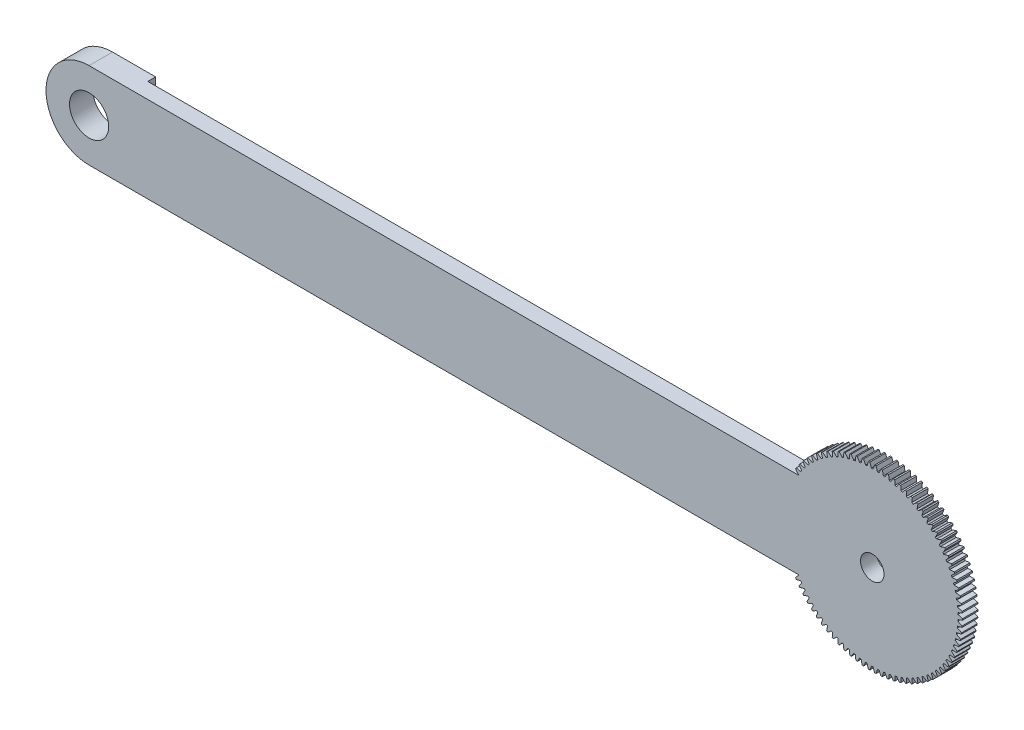
SolidWorks part; units mm, degrees
material "Alumina"
ref_plane "Plane1" through (0, 0, 0) normal (0, 0, 1) x (1, 0, 0)
ref_plane "Plane2" through (0, 0, 0) normal (0, 1, 0) x (1, 0, 0)
ref_plane "Plane3" through (0, 0, 0) normal (1, 0, 0) x (0, 0, -1)
sketch "HoldingSke" plane through (0, 0, 0) normal (0, 1, 0) x (1, 0, 0)
  line L0 (0, 0) -> (0, -2)
  line L1 (-15, 0) -> (100, 0) construction
  line L2 (0, 0) -> (-2.1039, 2.3779)
  line L3 (0, 0) -> (-11.863, 4.5341)
  line L4 (0, 0) -> (0, 8.636)
  line L5 (0, 0) -> (-46.8476, -17.4728)
  line L6 (0, 0) -> (-3.3159, -2.2372)
  line L7 (-2.1039, 2.3779) -> (8.6586, 51.2059)
  line L8 (-76.2, 54.61) -> (-74.4, 54.61)
  line L9 (-71.009, 38.7566) -> (-53.1078, 45.2721)
  line L10 (-76.2, 71.12) -> (104.1128, 71.12)
  line L11 (0, 0) -> (-4, 0)
  line L12 (-76.2, 101.6) -> (-76.181, 101.6)
  line L13 (24.9733, 27.94) -> (52.9518, 28.4284)
  line L14 (24.9733, 27.94) -> (24.9743, 27.94)
  line L15 (24.9733, 27.94) -> (100.4006, 29.5858)
  line L16 (-63.627, -0.5) -> (-12.827, -0.5)
  circle A0 centre (0, 0) radius 5
  circle A1 centre (0, 0) radius 21.874
  circle A2 centre (0, 0) radius 37.5
  circle A3 centre (0, 0) radius 5
  dimension "MHD" = 43.748
  dimension "Hub_dia" = 75
  dimension "Bore" = 10
  dimension "MBD" = 10
  dimension "Num_teeth" = 90
  dimension "Pitch" = 2
  dimension "Overall_len" = 50
  dimension "Show_teeth" = 90
  dimension "Thickness" = 4
  dimension "OAL" = 50.0001
  dimension "T_dim" = 1.8
  dimension "Ap" = 20
  dimension "H" = 19.05
  dimension "Pitch_radius" = 180.3128
  dimension "Width" = 4
  dimension "Backlash" = 0.019
  dimension "Addendum_fac" = 1
  dimension "Dedendum_fac" = 1.25
  dimension "Clearance_fac" = 0.25
  dimension "Dedendum_add" = 0.001
  dimension "Module" = 0.5
sketch "BasProSke" plane through (0, 0, 0) normal (0, 1, 0) x (1, 0, 0)
  line L0 (-10, 0) -> (60, 0) construction
  line L1 (0, 0) -> (0, 23)
  line L2 (0, 0) -> (4, 0)
  line L3 (4, 0) -> (4, 23)
  line L4 (4, 23) -> (0, 23)
  dimension "Thickness" = 4
  dimension "Diameter" = 46
revolve "Base-Revolve" add sketch "BasProSke" angle 360 about L0
sketch "TooCutSke" plane through (0, 0, 0) normal (1, 0, 0) x (0, 0, -1)
  line L1 (0, 0) -> (0, 107) construction
  line L2 (0, 0) -> (-0.4259, 22.496) construction
  line L3 (0, 0) -> (-1.5703, 44.9668) construction
  line L4 (-0.4259, 22.496) -> (-0.7851, 22.4834) construction
  arc A0 (0.2085, 21.873) -> (-0.2085, 21.873) centre (0, 0) ccw
  arc A1 (0.6483, 23.0163) -> (-0.6483, 23.0163) centre (0, 0) ccw
  circle A2 centre (0, 0) radius 22.5 construction
  circle A3 centre (0, 0) radius 21.1431 construction
  arc A4 (-0.2085, 21.873) -> (-0.6483, 23.0163) centre (-8.8088, 19.2207) ccw
  arc A5 (0.6483, 23.0163) -> (0.2085, 21.873) centre (8.8088, 19.2207) ccw
  dimension "Root_dia" = 43.748
  dimension "Overcut_dia" = 46.0508
  dimension "Pitch_dia" = 45
  dimension "Base_dia" = 42.2862
  dimension "Flank_rad" = 9
  dimension "Half_ang" = 2
  dimension "Half_CT" = 0.3594
extrude "ToothCut" cut sketch "TooCutSke" along normal through all
fillet "Breaks" [suppressed] radius 0.01 tangent propagation no
fillet "RootFillets" [suppressed] radius 0.126
pattern_circular "TeethCuts" count 90 every 4 about axis through (-10, 0, 0) along (1, 0, 0) of "ToothCut", "RootFillets", "Breaks"
sketch "HubNeaOneSke" plane through (0, 0, 0) normal (-1, 0, 0) x (0, 0, 1)
  circle A0 centre (0, 0) radius 21.874
  dimension "Diameter" = 43.748
extrude "HubNearOne" [suppressed] add sketch "HubNeaOneSke" along normal blind 46.0001
sketch "HubNeaBotSke" plane through (0, 0, 0) normal (-1, 0, 0) x (0, 0, 1)
  circle A0 centre (0, 0) radius 21.874
  dimension "Diameter" = 43.748
extrude "HubNearBoth" [suppressed] add sketch "HubNeaBotSke" along normal blind 23
ref_plane "FarPln" through (4, 0, 0) normal (1, 0, 0) x (0, 0, -1)
sketch "HubFarSke" plane through (4, 0, 0) normal (1, 0, 0) x (0, 0, -1)
  circle A0 centre (0, 0) radius 21.874
  dimension "Diameter" = 43.748
extrude "HubFar" [suppressed] add sketch "HubFarSke" along normal blind 23
sketch "BorSke" plane through (0, 0, 0) normal (1, 0, 0) x (0, 0, -1)
  circle A0 centre (0, 0) radius 5
  dimension "Diameter" = 10
extrude "Bore" cut sketch "BorSke" along normal mid plane 100.0001
sketch "KeySke" plane through (0, 0, 0) normal (1, 0, 0) x (0, 0, -1)
  line L0 (-2, 0) -> (-2, 6.8)
  line L1 (-2, 6.8) -> (2, 6.8)
  line L2 (2, 6.8) -> (2, 0)
  line L3 (0, 0) -> (0, 34) construction
  line L4 (-2, 0) -> (2, 0)
  dimension "Width" = 4
  dimension "Offset" = 6.8
extrude "Keyway" [suppressed] cut sketch "KeySke" along normal mid plane 100.0001
pattern_circular "Keyway2" [suppressed] count 2 every 90 about axis through (-10, 0, 0) along (1, 0, 0) reverse direction yes
sketch "Sketch1" plane through (0, 0, 0) normal (1, 0, 0) x (0, 0, -1)
  line L0 (0, 0) -> (-200, 0) construction
  line L1 (0, -11) -> (-200, -11)
  line L2 (0, 11) -> (-200, 11)
  arc A0 (0, -11) -> (0, 11) centre (0, 0) ccw
  arc A1 (-200, 11) -> (-200, -11) centre (-200, 0) ccw
  point P3 (-100, 0)
extrude "Boss-Extrude1" add sketch "Sketch1" along normal blind 4 contours L2 A1 L1 A0
sketch "Sketch3" plane through (0, 0, 0) normal (1, 0, 0) x (0, 0, -1)
  circle A2 centre (-200, 0) radius 5
extrude "Cut-Extrude2" cut sketch "Sketch3" along normal through all contours A2 region at (0, 0, 200)
sketch "Sketch4" plane through (0, 0, 0) normal (1, 0, 0) x (0, 0, -1)
  circle A0 centre (0, 0) radius 3
extrude "Cut-Extrude4" cut sketch "Sketch4" along normal through all
move or copy body "Body-Move/Copy1" bodies to move or copy 106 copy no rotation origin (2, 0, 94) rotation axis (0, 1, 0) rotation angle 90
move or copy body "Body-Move/Copy2" bodies to move or copy 107 copy no rotation origin (2, 0, 0) rotation axis (0, 0, 1) rotation angle 180
sketch "Sketch5" plane through (0, 0, 92) normal (0, 0, -1) x (-1, 0, 0)
  line L1 (93, 11) -> (93, -11)
  line L2 (-77.0931, 11) -> (104, 11) construction
  line L3 (-77.0931, -11) -> (104, -11) construction
  line L4 (93, 11) -> (104, 11)
  line L5 (93, -11) -> (104, -11)
  arc A1 (104, -11) -> (104, 11) centre (104, 0) ccw construction
  circle A2 centre (104, 0) radius 5 construction
  circle A3 centre (104, 0) radius 5
  arc A4 (104, -11) -> (104, 11) centre (104, 0) ccw
extrude "Boss-Extrude2" add sketch "Sketch5" along normal blind 2
ref_axis "Axis1" through (96, 0, 63.756) along (0, 0, 1)
equation "' \"Module@HoldingSke\" = 6.35"
equation "' \"Num_teeth@HoldingSke\" = 12"
equation "' \"Ap@HoldingSke\" =  20"
equation "' \"Ap@HoldingSke\" = 20"
equation "' \"Width@HoldingSke\" = 0.5 * 25.4"
equation "' \"Hub_dia@HoldingSke\"= 1 * 25.4"
equation "' \"Hub_dia@HoldingSke\" = 1 * 25.4"
equation "' \"Overall_len@HoldingSke\" = 1.0 * 25.4"
equation "' \"Bore@HoldingSke\" = 0.75 * 25.4"
equation "' \"T_dim@HoldingSke\" = 0.1 * 25.4"
equation "' \"Width@KeySke\" = 0.25 * 25.4"
equation "' \"Show_teeth@HoldingSke\" = 13"
equation "' \"Backlash@HoldingSke\" = 0.009 * 25.4"
equation "' \"Addendum_fac@HoldingSke\" = 1.0"
equation "' \"Dedendum_fac@HoldingSke\" = 1.25"
equation "' \"Dedendum_add@HoldingSke\" = 0.00005 * 25.4"
equation "' \"Clearance_fac@HoldingSke\" = 0.25"
equation "\"Pitch@HoldingSke\" = 1 / \"Module@HoldingSke\""
equation "\"Overcut_dia@TooCutSke\" = (\"Num_teeth@HoldingSke\" + 2 * \"Addendum_fac@HoldingSke\") / \"Pitch@HoldingSke\" + 0.002 * 25.4"
equation "\"Pitch_dia@TooCutSke\" = \"Num_teeth@HoldingSke\" / \"Pitch@HoldingSke\""
equation "\"Base_dia@TooCutSke\" = \"Num_teeth@HoldingSke\" / \"Pitch@HoldingSke\" * cos((\"Ap@HoldingSke\"  * 3.14159265 / 180))"
equation "\"Root_dia@TooCutSke\" = (\"Num_teeth@HoldingSke\" + 2) / \"Pitch@HoldingSke\" - 2 * (\"Addendum_fac@HoldingSke\" + \"Dedendum_fac@HoldingSke\") / \"Pitch@HoldingSke\" - \"Dedendum_add@HoldingSke\" * 2"
equation "\"Half_ang@TooCutSke\" = 180 / \"Num_teeth@HoldingSke\""
equation "\"Half_CT@TooCutSke\" = \"Num_teeth@HoldingSke\" / \"Pitch@HoldingSke\" * sin((3.14159265 / 2 / \"Num_teeth@HoldingSke\")) / 2 - 7 * \"Backlash@HoldingSke\" / 4"
equation "\"Flank_rad@TooCutSke\" = \"Num_teeth@HoldingSke\" / \"Pitch@HoldingSke\" / 5"
equation "\"Radius@RootFillets\" = \"Clearance_fac@HoldingSke\" / \"Pitch@HoldingSke\" + \"Dedendum_add@HoldingSke\""
equation "\"Break_rad@Breaks\" = 0.02 / \"Pitch@HoldingSke\""
equation "\"Thickness@HoldingSke\" = \"Width@HoldingSke\""
equation "\"OAL@HoldingSke\" = \"Thickness@HoldingSke\""
equation "\"MHD@HoldingSke\" = (\"Num_teeth@HoldingSke\" + 2) / \"Pitch@HoldingSke\" - 2 * (\"Addendum_fac@HoldingSke\" + \"Dedendum_fac@HoldingSke\")  / \"Pitch@HoldingSke\" - \"Dedendum_add@HoldingSke\" * 2"
equation "\"MBD@HoldingSke\" = (\"Num_teeth@HoldingSke\" + 2) / \"Pitch@HoldingSke\" - 2 * (\"Addendum_fac@HoldingSke\" + \"Dedendum_fac@HoldingSke\")  / \"Pitch@HoldingSke\" - \"Dedendum_add@HoldingSke\" * 2 - 0.002 * 25.4"
equation "\"MHD@HoldingSke\" = ((sgn( \"MHD@HoldingSke\" - \"Hub_dia@HoldingSke\" )-1)*( \"MHD@HoldingSke\" - \"Hub_dia@HoldingSke\" ))/-2+ \"Hub_dia@HoldingSke\""
equation "\"MBD@HoldingSke\" = ((sgn( \"MBD@HoldingSke\" - \"Bore@HoldingSke\" )-1)*( \"MBD@HoldingSke\" - \"Bore@HoldingSke\" ))/-2+ \"Bore@HoldingSke\""
equation "\"OAL@HoldingSke\" = ((sgn( \"OAL@HoldingSke\" - \"Overall_len@HoldingSke\" )+1)*( \"OAL@HoldingSke\" - \"Overall_len@HoldingSke\" ))/2 + \"Overall_len@HoldingSke\" + 0.000002 * 25.4"
equation "\"Num_teeth@TeethCuts\" = int( \"Show_teeth@HoldingSke\" ) + 1"
equation "\"Num_teeth@TeethCuts\" = ((sgn( \"Num_teeth@TeethCuts\" - \"Num_teeth@HoldingSke\" )-1)*( \"Num_teeth@TeethCuts\" - \"Num_teeth@HoldingSke\" ))/-2+ \"Num_teeth@HoldingSke\""
equation "\"Num_teeth@TeethCuts\" = ((sgn( \"Num_teeth@TeethCuts\" - 2.0)+1)*( \"Num_teeth@TeethCuts\" - 2.0))/2 +2.0"
equation "\"Angle@TeethCuts\" = 360.0 / \"Num_teeth@HoldingSke\""
equation "\"Diameter@BasProSke\" = (\"Num_teeth@HoldingSke\" + 2 * \"Addendum_fac@HoldingSke\") / \"Pitch@HoldingSke\""
equation "\"Thickness@BasProSke\"  = \"Thickness@HoldingSke\""
equation "' \"Fillet_rad@BasProSke\" =  \"Thickness@HoldingSke\" * 0.05"
equation "' \"Fillet_rad@BasProSke\" = \"Thickness@HoldingSke\" * 0.05"
equation "\"MHD@HoldingSke\" = ((sgn( \"MHD@HoldingSke\" - \"Root_dia@TooCutSke\" )-1)*( \"MHD@HoldingSke\" - \"Root_dia@TooCutSke\" ))/-2+ \"Root_dia@TooCutSke\""
equation "\"Diameter@HubNeaOneSke\" = \"MHD@HoldingSke\""
equation "\"Length@HubNearOne\" = \"OAL@HoldingSke\" - \"Thickness@BasProSke\""
equation "\"Diameter@HubNeaBotSke\" = \"MHD@HoldingSke\""
equation "\"Length@HubNearBoth\" = ( \"OAL@HoldingSke\" - \"Thickness@BasProSke\" ) / 2.0"
equation "\"Thickness@FarPln\" = \"Thickness@BasProSke\""
equation "\"Diameter@HubFarSke\" = \"MHD@HoldingSke\""
equation "\"Length@HubFar\" = ( \"OAL@HoldingSke\" - \"Thickness@BasProSke\" ) / 2.0"
equation "\"Diameter@BorSke\" = \"MBD@HoldingSke\""
equation "\"D1@Bore\" = \"OAL@HoldingSke\" * 2.0"
equation "\"D1@Keyway\" = \"OAL@HoldingSke\" * 2.0"
equation "\"Offset@KeySke\" = \"T_dim@HoldingSke\" + \"MBD@HoldingSke\" / 2.0"
